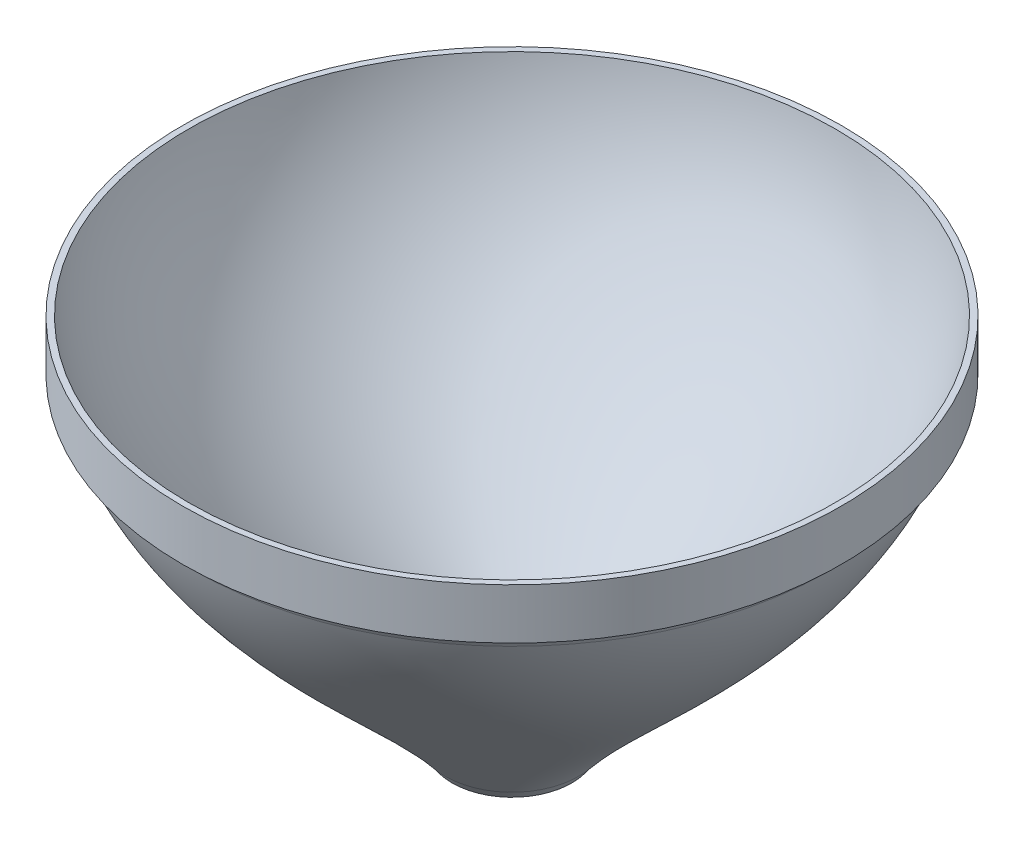
SolidWorks part; units mm, degrees
ref_plane "Płaszczyzna przednia" through (0, 0, 0) normal (0, 0, 1) x (1, 0, 0)
ref_plane "Płaszczyzna górna" through (0, 0, 0) normal (0, 1, 0) x (1, 0, 0)
ref_plane "Płaszczyzna prawa" through (0, 0, 0) normal (1, 0, 0) x (0, 0, -1)
sketch "Sketch1" plane through (0, 0, 0) normal (0, 0, 1) x (1, 0, 0)
  line L0 (-20.1658, 177.6565) -> (-20.1658, 45.3185)
  line L1 (-20.1658, 45.3185) -> (-18.1658, 45.3185)
  line L2 (-18.1658, 45.3185) -> (-18.1658, 175.6565)
  line L3 (-18.1658, 175.6565) -> (-4.1658, 175.6565)
  line L4 (-4.1658, 175.6565) -> (-4.1658, 174.0528)
  line L5 (-4.1658, 174.0528) -> (-2.6658, 174.0528)
  line L6 (-2.6658, 174.0528) -> (-2.6658, 175.6565)
  line L8 (24.8342, 176.1565) -> (24.8342, 177.6565)
  line L10 (-2.6658, 177.1565) -> (-2.6658, 182.6565)
  line L11 (-2.6658, 182.6565) -> (-4.1658, 182.6565)
  line L12 (-4.1658, 182.6565) -> (-4.1658, 177.6565)
  line L13 (-4.1658, 177.6565) -> (-20.1658, 177.6565)
  line L15 (24.8342, 148.4714) -> (24.8342, -40.5547) construction
  line L16 (-4.1658, 177.6565) -> (-4.1658, 175.6565)
  line L17 (-3.9845, 53.8719) -> (56.7742, 96.4156)
  line L21 (56.7742, 96.4156) -> (56.7742, 93.974)
  line L22 (56.7742, 93.974) -> (-3.4255, 51.8217)
  line L26 (18.8342, 85.6565) -> (16.872, 85.6565)
  line L30 (-18.1658, 128.7465) -> (-18.9658, 128.7465)
  line L32 (-18.1658, 135.4565) -> (-18.9658, 135.4565)
  line L33 (-18.9658, 135.4565) -> (-18.9658, 128.7465)
  line L34 (-18.1658, 128.5465) -> (-19.1658, 128.5465)
  line L35 (-19.1658, 128.5465) -> (-19.1658, 135.6565)
  line L36 (-19.1658, 135.6565) -> (-18.1658, 135.6565)
  line L37 (-2.6658, 177.1565) -> (-2.6658, 175.6565)
  line L38 (-17.5576, 127.3754) -> (-17.5576, 127.3754)
  line L39 (-17.5576, 127.3754) -> (-17.5576, 127.3754)
  line L40 (-17.5576, 127.3754) -> (-17.5576, 127.3754)
  line L41 (15.9828, 86.8645) -> (16.872, 85.6565)
  line L42 (-17.5576, 127.3754) -> (-18.1658, 128.7465)
  line L43 (15.9828, 86.8645) -> (15.9828, 86.8645) construction
  spline S0 degree 3 poles (-18.1658, 135.4565) (-14.4546, 112.7695) (7.6229, 100.7425) (18.8342, 85.6565) knots 0 0 0 0 1 1 1 1
  spline S1 degree 1 poles (-17.5576, 127.3754) (15.9828, 86.8645) knots 0 0 1 1 construction
  spline S2 degree 3 poles (-17.5576, 127.3754) (-17.1493, 126.2825) (-16.2379, 124.1197) (-14.13, 120.0244) (-9.7541, 113.3263) (-3.6348, 106.5855) (2.7798, 100.3454) (7.5389, 95.8197) (11.2889, 92.1067) (14.0705, 89.1159) (15.3533, 87.63) (15.9828, 86.8645) knots 0.117145 0.117145 0.117145 0.117145 0.169312 0.221479 0.325814 0.534482 0.638817 0.743151 0.847485 0.899652 0.95182 0.95182 0.95182 0.95182
  point P17 (16.872, 85.6565)
  dimension "D1" = 2
  dimension "D3" = 2
  dimension "D4" = 5
  dimension "D5" = 1.5
  dimension "D6" = 45
  dimension "D2" = 0.2
  dimension "D10" = 0.2
  dimension "D11" = 0.2
  dimension "D7" = 6
  dimension "D12" = 7.11
  dimension "D8" = 1
  dimension "D13" = 40
  dimension "D14" = 90
  dimension "D9" = 1.5
revolve "Revolve1" add sketch "Sketch1" angle 360 about L15 region at (-18.5658, 132.1015, 0) region at (-17.5454, 132.1015, 0)
equation "\"outerdiameter\"= 45"
equation "\"D6@Sketch1\"=\"outerdiameter\""
equation "\"wallthick\"= 2"
equation "\"D1@Sketch1\"=\"wallthick\""
equation "\"D3@Sketch1\"=\"wallthick\""
